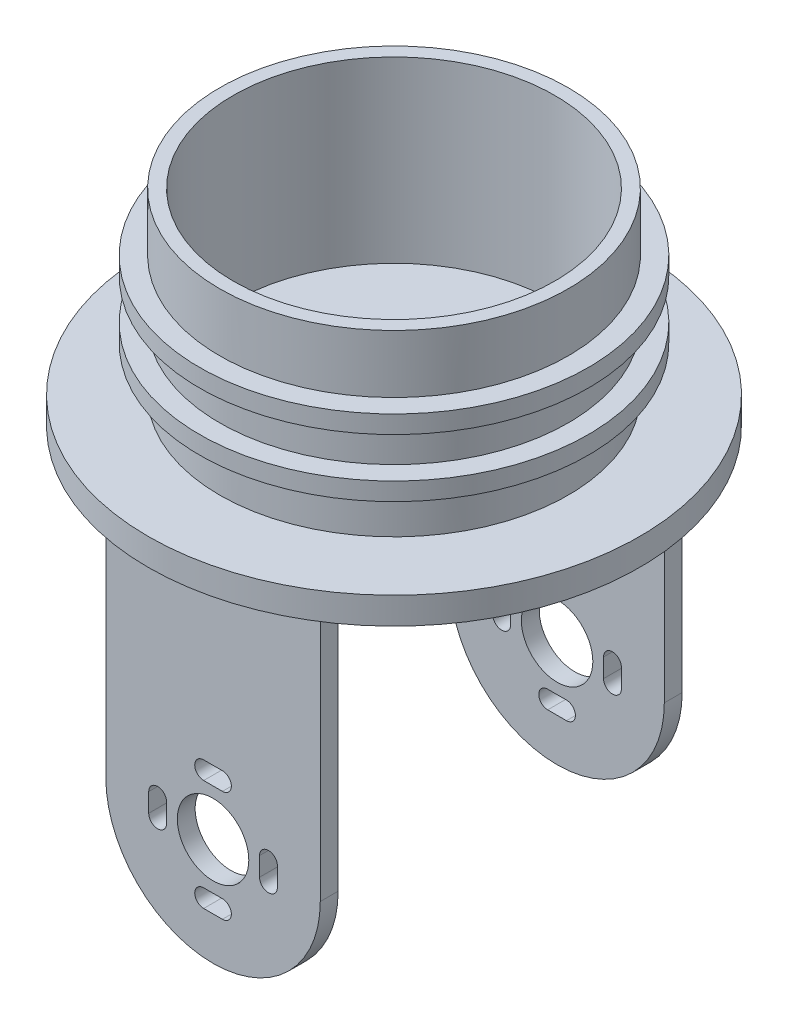
SolidWorks part; units mm, degrees
ref_plane "前基準面" through (0, 0, 0) normal (0, 0, 1) x (1, 0, 0)
ref_plane "上基準面" through (0, 0, 0) normal (0, 1, 0) x (1, 0, 0)
ref_plane "右基準面" through (0, 0, 0) normal (1, 0, 0) x (0, 0, -1)
sketch "草圖1" plane through (0, 0, 0) normal (0, 1, 0) x (1, 0, 0)
  circle A0 centre (0, 0) radius 19.5
  circle A1 centre (0, 0) radius 18
  dimension "D1" = 39
  dimension "D2" = 36
extrude "填料-伸長1" add sketch "草圖1" along normal blind 20
sketch "草圖3" plane through (0, 0, 0) normal (0, -1, 0) x (1, 0, 0)
  circle A0 centre (0, 0) radius 27.5
  dimension "D1" = 55
extrude "填料-伸長2" add sketch "草圖3" along normal blind 3
sketch "草圖4" plane through (0, 0, 0) normal (0, 0, 1) x (1, 0, 0)
  line L0 (0, 20) -> (0, -52.6673) construction
  line L1 (18, 20) -> (-18, 20) construction
  line L2 (-27.5, -3) -> (27.5, -3) construction
  line L3 (-10, -3) -> (10, -3)
  line L4 (-10, -3) -> (-10, -63)
  line L5 (-10, -63) -> (10, -63)
  line L6 (10, -3) -> (10, -63)
  line L8 (-6.5, -28) -> (6.5, -28)
  line L9 (-6.5, -28) -> (-6.5, -53)
  line L10 (-6.5, -53) -> (6.5, -53)
  line L11 (6.5, -28) -> (6.5, -53)
  dimension "D1" = 10
  dimension "D2" = 10
  dimension "D3" = 60
  dimension "D4" = 6.5
  dimension "D5" = 6.5
  dimension "D6" = 25
  dimension "D7" = 25
ref_plane "平面2" through (0, -3, 0) normal (0, -1, 0) x (-1, 0, 0)
ref_plane "平面5" through (0, 0, 0) normal (0, 1, 0) x (1, 0, 0)
ref_plane "平面6" through (0, 7, 0) normal (0, -1, 0) x (-1, 0, 0)
sketch "草圖25" plane through (0, 7, 0) normal (0, -1, 0) x (-1, 0, 0)
  circle A0 centre (0, 0) radius 21.75
  circle A1 centre (0, 0) radius 19.5
  dimension "D1" = 43.5
extrude "填料-伸長12" add sketch "草圖25" along normal blind 2
ref_plane "平面10" through (0, 10.5, 0) normal (0, -1, 0) x (-1, 0, 0)
sketch "草圖26" plane through (0, 10.5, 0) normal (0, -1, 0) x (-1, 0, 0)
  circle A0 centre (0, 0) radius 21.75
  circle A1 centre (0, 0) radius 19.5
extrude "填料-伸長13" add sketch "草圖26" against normal blind 2 from offset 1 offset against normal yes
ref_plane "平面11" through (0, -3, 0) normal (0, -1, 0) x (-1, 0, 0)
sketch "草圖27" plane through (0, -3, 0) normal (0, -1, 0) x (-1, 0, 0)
  line L0 (-27.5, 0) -> (27.5, 0) construction
  line L1 (-12, 20.25) -> (12, 20.25)
  line L2 (-12, 20.25) -> (-12, 18.25)
  line L3 (-12, 18.25) -> (12, 18.25)
  line L4 (12, 20.25) -> (12, 18.25)
  line L5 (-46.0389, 0) -> (46.0389, 0) construction
  line L6 (0, 0) -> (0, -33.56) construction
  line L7 (-12, -18.25) -> (12, -18.25)
  line L8 (12, -20.25) -> (12, -18.25)
  line L9 (-12, -20.25) -> (12, -20.25)
  line L10 (-12, -20.25) -> (-12, -18.25)
  circle A0 centre (0, 0) radius 27.5 construction
  point P13 (-12, 19.25)
  dimension "D1" = 18.25
  dimension "D2" = 24
  dimension "D3" = 12
  dimension "D4" = 2
ref_plane "平面12" through (0, 0, -18.25) normal (0, 0, 1) x (1, 0, 0)
sketch "草圖28" plane through (0, 0, -18.25) normal (0, 0, 1) x (1, 0, 0)
  line L0 (0, -3) -> (0, -48.9232) construction
  line L1 (12, -3) -> (-12, -3) construction
  line L2 (12, -3) -> (-12, -3) construction
  line L3 (-12, -3) -> (12, -3)
  line L4 (-12, -3) -> (-12, -33)
  line L6 (12, -3) -> (12, -33)
  line L7 (-12, -33) -> (12, -33) construction
  line L8 (-1.05, -26.8) -> (1.05, -26.8) construction
  line L9 (-1.05, -25.8) -> (1.05, -25.8)
  line L10 (-1.05, -27.8) -> (1.05, -27.8)
  line L11 (6.2, -31.95) -> (6.2, -34.05) construction
  line L12 (7.2, -31.95) -> (7.2, -34.05)
  line L13 (5.2, -31.95) -> (5.2, -34.05)
  line L14 (-1.05, -39.2) -> (1.05, -39.2) construction
  line L15 (-1.05, -40.2) -> (1.05, -40.2)
  line L16 (-1.05, -38.2) -> (1.05, -38.2)
  line L17 (-6.2, -31.95) -> (-6.2, -34.05) construction
  line L18 (-7.2, -31.95) -> (-7.2, -34.05)
  line L19 (-5.2, -31.95) -> (-5.2, -34.05)
  arc A1 (-12, -33) -> (12, -33) centre (0, -33) ccw
  circle A2 centre (0, -33) radius 4
  arc A3 (-1.05, -25.8) -> (-1.05, -27.8) centre (-1.05, -26.8) ccw
  arc A4 (1.05, -27.8) -> (1.05, -25.8) centre (1.05, -26.8) ccw
  arc A5 (7.2, -31.95) -> (5.2, -31.95) centre (6.2, -31.95) ccw
  arc A6 (5.2, -34.05) -> (7.2, -34.05) centre (6.2, -34.05) ccw
  arc A7 (-1.05, -40.2) -> (-1.05, -38.2) centre (-1.05, -39.2) cw
  arc A8 (1.05, -38.2) -> (1.05, -40.2) centre (1.05, -39.2) cw
  arc A9 (-7.2, -31.95) -> (-5.2, -31.95) centre (-6.2, -31.95) cw
  arc A10 (-5.2, -34.05) -> (-7.2, -34.05) centre (-6.2, -34.05) cw
  point P15 (0, -26.8)
  point P20 (6.2, -33)
  point P27 (0, 0)
  point P28 (0, 0)
  point P29 (0, 0)
  point P32 (0, -39.2)
  point P39 (-6.2, -33)
  dimension "D2" = 0
  dimension "D10" = 8
  dimension "D1" = 30
  dimension "D3" = 0
  dimension "D4" = 6.2
  dimension "D5" = 6.2
  dimension "D6" = 2.1
  dimension "D7" = 2
  dimension "D8" = 2.1
  dimension "D9" = 2
extrude "填料-伸長14" add sketch "草圖28" against normal blind 2
pattern_linear "直線複製排列1" count 2 spacing 38.5 along (0, 0, 1) of "填料-伸長14"
